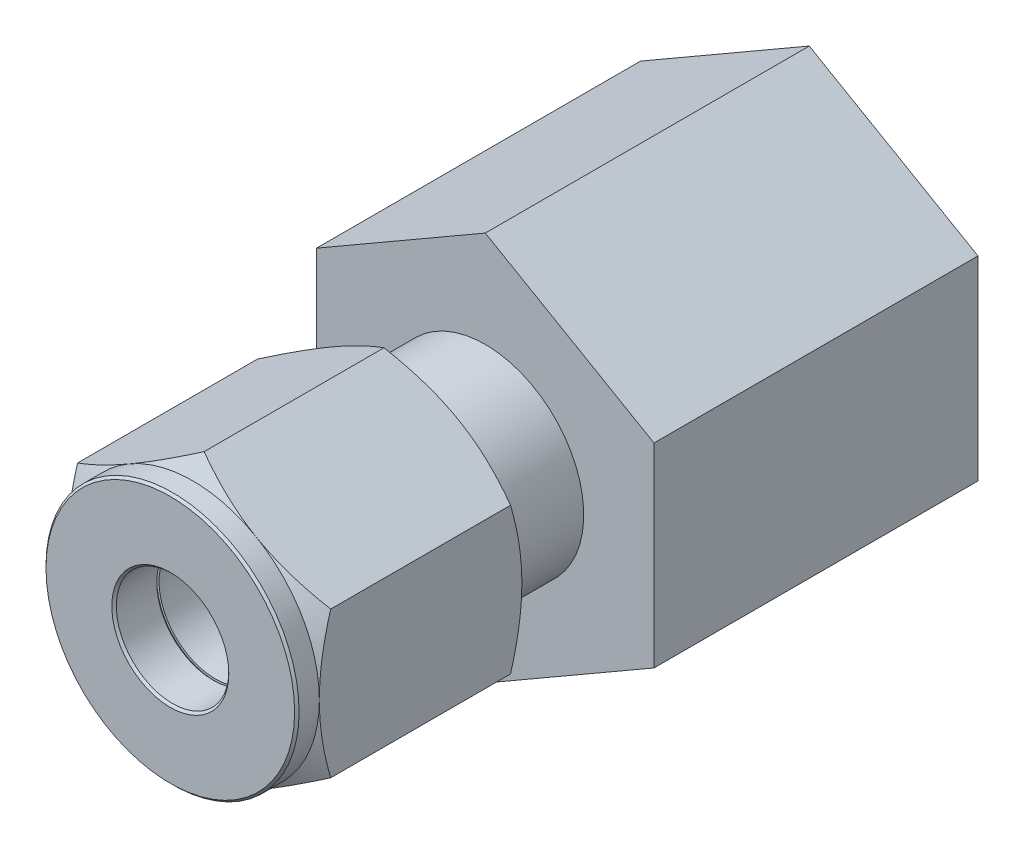
SolidWorks part; units mm, degrees
ref_plane "Front Plane" through (0, 0, 0) normal (0, 0, 1) x (1, 0, 0)
ref_plane "Top Plane" through (0, 0, 0) normal (0, 1, 0) x (1, 0, 0)
ref_plane "Right Plane" through (0, 0, 0) normal (1, 0, 0) x (0, 0, -1)
sketch "Sketch1" plane through (0, 0, 0) normal (1, 0, 0) x (0, 0, -1)
  line L0 (0, 0) -> (36.068, 0) construction
  line L1 (0, 3.175) -> (0, -3.175) construction
  line L2 (12.7, 7.1437) -> (12.7, -7.1437) construction
  line L3 (5.08, 5.5562) -> (5.08, -5.5562) construction
  line L4 (5.08, 5.5562) -> (5.08, 4.2862) construction
  line L5 (17.78, 9.525) -> (17.78, -9.525) construction
  line L6 (4.445, 4.699) -> (9.3218, 3.6068) construction
  line L7 (9.3218, 3.6068) -> (9.3218, 3.175) construction
  line L8 (9.3218, 3.175) -> (5.1308, 3.175) construction
  line L9 (5.1308, 3.175) -> (4.445, 3.8608) construction
  line L10 (4.445, 3.8608) -> (4.445, 4.699) construction
  line L11 (2.54, 4.6609) -> (3.556, 4.6609) construction
  line L12 (3.556, 4.6609) -> (3.556, 3.8608) construction
  line L13 (3.556, 3.8608) -> (4.445, 3.8608) construction
  line L14 (17.78, 2.3749) -> (17.78, -2.3749) construction
  line L15 (4.445, 3.8608) -> (4.445, 3.175) construction
  line L16 (5.1308, 3.175) -> (2.54, 3.175) construction
  line L17 (2.54, 3.175) -> (2.54, 4.6609) construction
  line L18 (4.445, 3.175) -> (5.1308, 3.175) construction
  line L19 (0, 3.175) -> (2.54, 3.175) construction
  line L20 (2.54, 3.175) -> (5.08, 3.175) construction
  line L21 (36.068, 6.858) -> (36.068, -6.858) construction
  line L22 (20.9652, 6.3878) -> (20.9652, -6.3878) construction
  line L23 (20.9652, 6.3878) -> (36.068, 6.858) construction
  line L24 (20.9652, 6.3878) -> (20.9652, 4.9767) construction
  line L25 (25.8623, 6.5402) -> (25.8623, -6.5402) construction
  line L26 (36.068, 4.6228) -> (36.068, -4.6228) construction
  point P4 (1.27, 0)
  point P10 (5.08, 0)
  point P12 (12.7, 0)
  point P15 (17.78, 0)
  point P16 (7.366, 0)
  point P17 (15.24, 0)
  point P40 (20.9652, 0)
  point P44 (25.8623, 0)
sketch "Sketch2" plane through (0, 0, 0) normal (0, 0, 1) x (1, 0, 0)
  line L0 (0, 3.175) -> (0, -3.175) construction
  line L1 (0, 8.2489) -> (-7.1437, 4.1244)
  line L2 (-7.1437, 4.1244) -> (-7.1438, -4.1244)
  line L3 (-7.1438, -4.1244) -> (0, -8.2489)
  line L4 (0, -8.2489) -> (7.1437, -4.1244)
  line L5 (7.1437, -4.1244) -> (7.1438, 4.1244)
  line L6 (7.1438, 4.1244) -> (0, 8.2489)
  line L7 (0, 8.2489) -> (0, 0) construction
  circle A0 centre (0, 0) radius 7.1438 construction
extrude "Boss-Extrude1" add sketch "Sketch2" against normal up to vertex (12.7 mm away) up to point (0, 0, -12.7)
sketch "Sketch3" plane through (0, 0, 0) normal (1, 0, 0) x (0, 0, -1)
  line L0 (0, 8.2489) -> (0, 7.1437)
  line L1 (0, 4.1244) -> (0, 8.2489) construction
  line L2 (0, 7.1437) -> (1.27, 7.1437)
  line L3 (1.27, 7.1437) -> (1.9081, 8.2489)
  line L4 (12.7, 8.2489) -> (0, 8.2489) construction
  line L5 (1.9081, 8.2489) -> (12.0619, 8.2489)
  line L6 (12.0619, 8.2489) -> (12.7, 7.1437)
  line L7 (12.7, 7.1437) -> (12.7, 8.2489)
  line L8 (12.7, 8.2489) -> (12.7, 9.354)
  line L9 (12.7, 9.354) -> (0, 9.354)
  line L10 (0, 9.354) -> (0, 8.2489)
  line L11 (0, 3.175) -> (0, 0)
  line L12 (0, 3.175) -> (0, -3.175) construction
  line L13 (0, 0) -> (12.7, 0)
  line L14 (12.7, 7.1437) -> (12.7, -7.1437) construction
  line L15 (12.7, 0) -> (12.7, 5.5562)
  line L16 (12.7, 5.5562) -> (5.08, 5.5562)
  line L17 (5.08, 5.5562) -> (5.08, 4.2862) construction
  line L18 (5.08, 4.2862) -> (2.54, 4.2862) construction
  line L19 (2.54, 4.2862) -> (2.54, 3.175)
  line L20 (2.54, 3.175) -> (0, 3.175)
  line L21 (2.54, 4.2862) -> (2.54, 5.5562) construction
  line L22 (2.54, 5.5562) -> (5.08, 5.5562) construction
  line L23 (5.08, 4.9212) -> (2.54, 4.9213)
  line L24 (2.54, 4.9213) -> (2.54, 4.2862)
  line L25 (5.08, 4.9212) -> (5.08, 5.5562)
  dimension "D1" = 30
  dimension "D2" = 1.27
revolve "Cut-Revolve1" cut sketch "Sketch3" angle 360 about L0
chamfer "Chamfer1" distance 0.127 angle 45 3 edges at (3.175, 0, -2.54) (3.175, 0, 0) (7.1437, 0, 0)
sketch "Sketch4" plane through (0, 0, 0) normal (1, 0, 0) x (0, 0, -1)
  line L1 (17.78, 0) -> (7.366, 0)
  line L2 (17.78, 0) -> (17.78, 5.5563)
  line L3 (17.78, 5.5563) -> (7.366, 5.5562)
  line L4 (7.366, 0) -> (7.366, 5.5562)
  dimension "D1" = 10.414
revolve "Revolve1" add sketch "Sketch4" angle 360 about L1
sketch "Sketch5" [suppressed] plane through (0, 0, -7.366) normal (0, 0, -1) x (-1, 0, 0)
  circle A0 centre (0, 0) radius 5.5562 construction
  circle A1 centre (0, 0) radius 5.5562
  point P3 (0, 5.5562)
curve "Helix/Spiral1" [suppressed] pitch 1.27 height 11.684 turns 9.2
sketch "Sketch6" [suppressed] plane through (0, 0, 0) normal (1, 0, 0) x (0, 0, -1)
  line L0 (6.1754, 5.6937) -> (7.4454, 5.6937) construction
  line L1 (7.4454, 5.6937) -> (6.8104, 4.5939) construction
  line L2 (6.8104, 4.5939) -> (6.1754, 5.6937) construction
  line L3 (6.731, 4.7314) -> (6.8898, 4.7314) construction
  line L4 (6.2548, 5.5563) -> (7.366, 5.5563) construction
  line L5 (6.8104, 4.5939) -> (6.8104, 4.7314) construction
  line L6 (6.8104, 5.5563) -> (6.8104, 5.6937) construction
  line L7 (6.731, 4.7314) -> (6.2151, 5.625)
  line L8 (6.2151, 5.625) -> (7.4057, 5.625)
  line L9 (7.4057, 5.625) -> (6.8898, 4.7314)
  line L10 (6.8898, 4.7314) -> (6.731, 4.7314)
  point P10 (6.8104, 5.625)
  dimension "D1" = 1.27
  dimension "D2" = 0.1588
sweep "Cut-Sweep1" [suppressed] cut profiles "Sketch6" path "Helix/Spiral1"
sketch "Sketch7" plane through (0, 0, -17.78) normal (0, 0, -1) x (-1, 0, 0)
  line L0 (0, 0) -> (0, 10.9985) construction
  line L1 (0, 10.9985) -> (-9.525, 5.4993)
  line L2 (-9.525, 5.4993) -> (-9.525, -5.4993)
  line L3 (-9.525, -5.4993) -> (0, -10.9985)
  line L4 (0, -10.9985) -> (9.525, -5.4993)
  line L5 (9.525, -5.4993) -> (9.525, 5.4993)
  line L6 (9.525, 5.4993) -> (0, 10.9985)
  circle A0 centre (0, 0) radius 9.525 construction
extrude "Boss-Extrude2" add sketch "Sketch7" along normal up to vertex (18.288 mm away) up to point (0, 0, -36.068)
sketch "Sketch8" [suppressed] plane through (0, 0, 0) normal (1, 0, 0) x (0, 0, -1)
  line L0 (7.366, 5.6937) -> (7.366, 4.5939)
  line L1 (7.366, 4.5939) -> (8.4659, 5.6937)
  line L2 (8.4659, 5.6937) -> (7.366, 5.6937)
  line L3 (17.78, 5.6937) -> (15.5803, 5.6937)
  line L4 (15.5803, 5.6937) -> (16.6801, 4.5939)
  line L5 (16.6801, 4.5939) -> (17.78, 4.5939)
  line L6 (17.78, 4.5939) -> (17.78, 5.6937)
  line L7 (36.068, 9.525) -> (35.2173, 10.9985)
  line L8 (36.068, 10.9985) -> (36.068, 5.4993) construction
  line L9 (36.068, 10.9985) -> (17.78, 10.9985) construction
  line L10 (35.2173, 10.9985) -> (18.6307, 10.9985)
  line L11 (15.24, 2.3749) -> (20.9652, 2.3749)
  line L12 (18.6307, 10.9985) -> (17.78, 9.525)
  line L14 (17.78, 10.9985) -> (17.78, 12.472)
  line L15 (17.78, 12.472) -> (36.068, 12.472)
  line L16 (36.068, 12.472) -> (36.068, 10.9985)
  line L17 (36.068, 10.9985) -> (36.068, 9.525)
  line L18 (6.8104, 4.5939) -> (7.366, 4.5939) construction
  line L19 (7.4454, 5.6937) -> (7.366, 5.6937) construction
  line L20 (8.4659, 5.6937) -> (15.5803, 5.6937) construction
  line L21 (16.6801, 4.5939) -> (7.366, 4.5939) construction
  line L22 (7.366, 4.0448) -> (11.2498, 3.175)
  line L23 (17.78, 9.525) -> (17.78, 10.9985)
  line L24 (7.366, 3.9289) -> (7.366, -4.7433) construction
  line L25 (4.445, 4.699) -> (9.3218, 3.6068) construction
  line L26 (20.9652, 0) -> (7.366, 0)
  line L27 (7.366, 0) -> (7.366, 4.0448)
  line L28 (11.2498, 3.175) -> (15.24, 3.175)
  line L29 (15.24, 3.175) -> (15.24, 2.3749)
  line L30 (20.9652, 2.3749) -> (20.9652, 0)
  line L31 (15.24, 0) -> (15.24, 2.3749) construction
  line L33 (36.068, 10.9985) -> (17.78, 10.9985) construction
  line L34 (17.78, 10.9985) -> (17.78, 5.4993) construction
  line L35 (17.78, 9.525) -> (17.78, -9.525) construction
  dimension "D1" = 30
revolve "Cut-Revolve2" [suppressed] cut sketch "Sketch8" angle 360 about L0
sketch "Sketch9" plane through (0, 0, 0) normal (1, 0, 0) x (0, 0, -1)
  line L0 (4.445, 4.699) -> (4.445, 3.8608)
  line L1 (4.445, 3.8608) -> (5.1308, 3.175)
  line L2 (5.1308, 3.175) -> (9.3218, 3.175)
  line L3 (9.3218, 3.175) -> (9.3218, 3.6068)
  line L4 (9.3218, 3.6068) -> (4.445, 4.699)
revolve "Revolve2" add sketch "Sketch9" angle 360 about L0
sketch "Sketch10" plane through (0, 0, 0) normal (1, 0, 0) x (0, 0, -1)
  line L0 (2.54, 4.6609) -> (3.556, 4.6609)
  line L1 (3.556, 4.6609) -> (3.556, 3.8608)
  line L2 (3.556, 3.8608) -> (4.445, 3.8608)
  line L4 (4.445, 3.8608) -> (5.1308, 3.175)
  line L5 (5.1308, 3.175) -> (2.54, 3.175)
  line L6 (2.54, 3.175) -> (2.54, 4.6609)
revolve "Revolve3" add sketch "Sketch10" angle 360 about L0
sketch "Sketch11" plane through (0, 0, 0) normal (1, 0, 0) x (0, 0, -1)
  line L0 (25.8623, 0) -> (36.068, 0)
  line L1 (36.068, 0) -> (36.068, 6.858)
  line L2 (36.068, 6.858) -> (25.8623, 6.5402)
  line L3 (25.8623, 6.5402) -> (25.8623, 0)
revolve "Revolve4" add sketch "Sketch11" angle 360 about L0
sketch "Sketch12" [suppressed] plane through (0, 0, -36.068) normal (0, 0, -1) x (-1, 0, 0)
  circle A1 centre (0, 0) radius 6.858
  circle A2 centre (0, 0) radius 6.858
  point P0 (0, 6.858)
  dimension "D1" = 0
curve "Helix/Spiral2" [suppressed]
sketch "Sketch13" [suppressed] plane through (0, 0, 0) normal (1, 0, 0) x (0, 0, -1)
  line L0 (35.9798, 7.0108) -> (37.3909, 7.0108) construction
  line L1 (35.9798, 7.0108) -> (36.6854, 5.7887) construction
  line L2 (36.6854, 5.7887) -> (37.3909, 7.0108) construction
  line L3 (36.5972, 5.9415) -> (36.7736, 5.9415) construction
  line L4 (36.068, 6.858) -> (37.3027, 6.858) construction
  line L5 (36.6854, 5.7887) -> (36.6854, 5.9415) construction
  line L6 (36.6854, 6.858) -> (36.6854, 7.0108) construction
  line L7 (36.6854, 6.9344) -> (37.3468, 6.9344) construction
  line L8 (36.6854, 5.7887) -> (36.6854, -6.8772) construction
  line L9 (36.6854, -6.8772) -> (35.2749, -6.8333) construction
  line L10 (35.2749, -6.8333) -> (33.8645, -6.7894) construction
  line L11 (33.8645, -6.7894) -> (32.4541, -6.7455) construction
  line L12 (35.9798, 7.0108) -> (37.3468, 6.9344)
  line L13 (37.3468, 6.9344) -> (36.7736, 5.9415)
  line L14 (36.7736, 5.9415) -> (36.5972, 5.9415)
  line L15 (36.5972, 5.9415) -> (35.9798, 7.0108)
  line L16 (25.8623, -6.5402) -> (36.068, -6.858) construction
  line L17 (32.4541, -6.7455) -> (31.0437, -6.7016) construction
  line L18 (31.0437, -6.7016) -> (29.6332, -6.6577) construction
  dimension "D1" = 1.4111
  dimension "D2" = 0.1764
sweep "Cut-Sweep2" [suppressed] cut profiles "Sketch13" path "Helix/Spiral2"
combine bodies "Combine1" operation type subtract main body 112 bodies to subtract 121
sketch "Sketch14" [suppressed] plane through (0, 0, 0) normal (1, 0, 0) x (0, 0, -1)
  line L0 (36.6854, 5.7887) -> (36.068, 5.7887) construction
  line L1 (36.068, 7.0108) -> (34.8459, 5.7887)
  line L2 (34.8459, 5.7887) -> (36.068, 5.7887)
  line L5 (36.068, 6.858) -> (36.068, -6.858) construction
  line L8 (36.068, 7.0108) -> (36.068, 5.7887)
  line L9 (35.9798, 7.0108) -> (37.3909, 7.0108) construction
  line L10 (36.068, 4.6228) -> (20.9652, 4.6228)
  line L11 (20.9652, 4.6228) -> (20.9652, 0) construction
  line L12 (18.1875, 0) -> (36.068, 0)
  line L13 (18.1875, 0) -> (20.9652, 4.6228)
  line L14 (36.068, 0) -> (36.068, 4.6228)
  dimension "D1" = 59
revolve "Cut-Revolve4" [suppressed] cut sketch "Sketch14" angle 360 about L0
equation "\"D4@Helix/Spiral1\" = \"Straight Thread Pitch@Sketch1\""
equation "\"D3@Helix/Spiral1\" = \"D4@Helix/Spiral1\" + \"D1@Sketch4\""
equation "\"D1@Sketch6\" = \"D4@Helix/Spiral1\""
equation "\"D2@Sketch6\" = \"D1@Sketch6\" / 8"
equation "\"D4@Helix/Spiral2\" = \"Pipe Pitch@Sketch1\""
equation "\"D3@Helix/Spiral2\" = \"D4@Helix/Spiral2\" + \"L4@Sketch1\""
equation "\"D1@Sketch13\" = \"D4@Helix/Spiral2\""
equation "\"D2@Sketch13\" = \"D1@Sketch13\" / 8"
